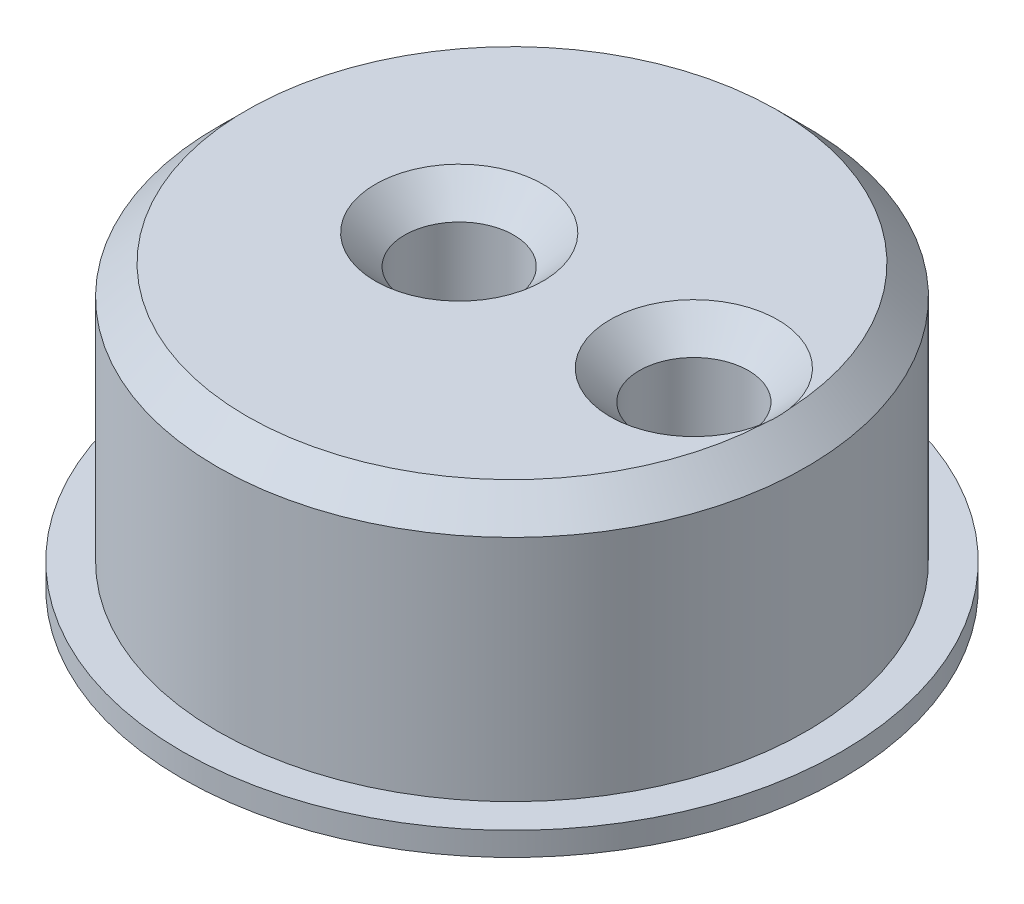
SolidWorks part; units mm, degrees
ref_plane "前视基准面" through (0, 0, 0) normal (0, 0, 1) x (1, 0, 0)
ref_plane "上视基准面" through (0, 0, 0) normal (0, 1, 0) x (1, 0, 0)
ref_plane "右视基准面" through (0, 0, 0) normal (1, 0, 0) x (0, 0, -1)
other "Configuration Table"
sketch "草图1" plane through (0, 0, 0) normal (0, 1, 0) x (1, 0, 0)
  line L0 (1.1, 6.4178) -> (1.1, -6.4114) construction
  line L1 (-5.7349, 0) -> (5.8104, 0) construction
  circle A0 centre (0, 0) radius 5.02
  circle A1 centre (3.1, 0) radius 0.93
  circle A2 centre (-0.9, 0) radius 0.93
  dimension "D1" = 10.04
  dimension "D3" = 4
  dimension "D4" = 1.86
  dimension "D2" = 1.1
extrude "凸台-拉伸1" add sketch "草图1" along normal blind 4.4
sketch "草图3" plane through (0, 0, 0) normal (0, -1, 0) x (1, 0, 0)
  circle A0 centre (3.1, 0) radius 0.93 construction
  circle A1 centre (0, 0) radius 5.02 construction
  circle A3 centre (-0.9, 0) radius 0.93 construction
  circle A4 centre (3.1, 0) radius 0.93
  circle A5 centre (-0.9, 0) radius 0.93
  circle A6 centre (0, 0) radius 5.02 construction
  circle A7 centre (0, 0) radius 5.62
  dimension "D1" = 0.6
extrude "凸台-拉伸2" add sketch "草图3" along normal blind 0.4
chamfer "倒角1" distance 0.5 angle 45 5 edges at (0, 4.4, 5.02) (-0.9, 4.4, -0.93) (3.1, 4.4, 0.93) (-0.9, -0.4, -0.93) (3.1, -0.4, -0.93)
ref_axis "基准轴1" through (0, 3.9, 0) along (0, -1, 0)
sketch "草图2" plane through (0, 0, 0) normal (0, 1, 0) x (1, 0, 0)
  line L0 (-5.9042, 0) -> (6.2358, 0) construction
